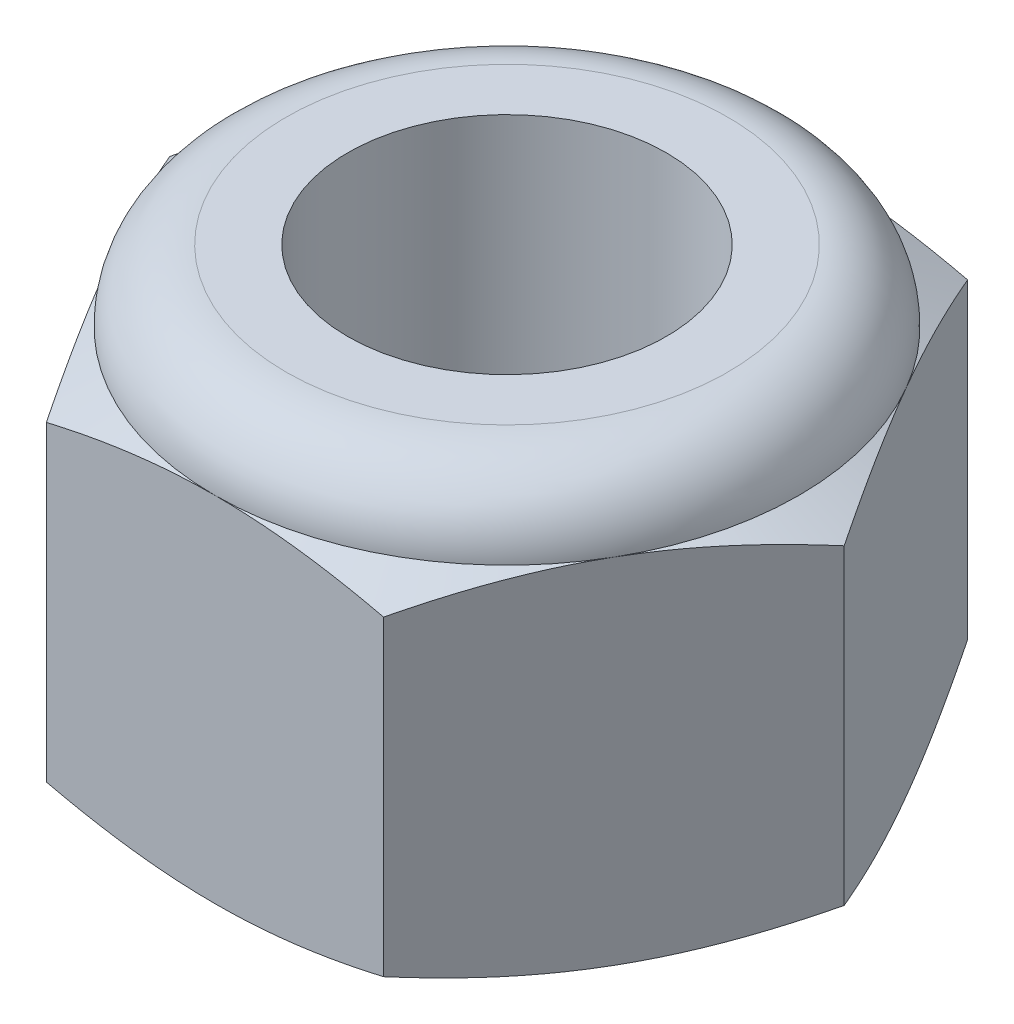
SolidWorks part; units mm, degrees
material "Stainless Steel (ferritic)"
ref_plane "Front" through (0, 0, 0) normal (0, 0, 1) x (1, 0, 0)
ref_plane "Top" through (0, 0, 0) normal (0, 1, 0) x (1, 0, 0)
ref_plane "Right" through (0, 0, 0) normal (1, 0, 0) x (0, 0, -1)
sketch "Sketch1" plane through (0, 0, 0) normal (0, 1, 0) x (1, 0, 0)
  line L1 (1.5877, 2.75) -> (-1.5877, 2.75)
  line L2 (-1.5877, 2.75) -> (-3.1754, 0)
  line L3 (-3.1754, 0) -> (-1.5877, -2.75)
  line L4 (-1.5877, -2.75) -> (1.5877, -2.75)
  line L5 (1.5877, -2.75) -> (3.1754, 0)
  line L6 (3.1754, 0) -> (1.5877, 2.75)
  circle A0 centre (0, 0) radius 2.75 construction
  circle A1 centre (0, 0) radius 1.5
  dimension "D2" = 3
  dimension "D1" = 5.5
extrude "Boss-Extrude1" add sketch "Sketch1" along normal blind 3.33
sketch "Sketch2" plane through (0, 3.33, 0) normal (0, 1, 0) x (1, 0, 0)
  circle A0 centre (0, 0) radius 2.75
  circle A1 centre (0, 0) radius 1.5 construction
  circle A2 centre (0, 0) radius 1.5
  dimension "D1" = 5.5
extrude "Boss-Extrude2" add sketch "Sketch2" along normal blind 0.67
fillet "Fillet1" radius 0.67 1 edges at (0, 4, 2.75)
sketch "Sketch3" plane through (-4.7631, 0, 0) normal (0, 0, -1) x (-1, 0, 0)
  line L0 (-1.5877, 3.33) -> (-1.5877, 3.1316)
  line L1 (-3.1754, 3.33) -> (-3.1754, 0) construction
  line L2 (-2.0131, 0) -> (-1.5877, 0.1984)
  line L3 (-3.1754, 1.665) -> (-1.5877, 1.665) construction
  line L4 (-1.5877, 3.33) -> (-1.5877, 0) construction
  line L5 (-1.5877, 0) -> (-1.5877, 0.1984)
  line L7 (-1.5877, 0) -> (-2.0131, 0)
  line L8 (-1.5877, 3.33) -> (-2.0131, 3.33)
  line L9 (-2.0131, 3.33) -> (-1.5877, 3.1316)
  dimension "D1" = 25
sketch "Sketch4" plane through (0, 0, 0) normal (0, 0, 1) x (1, 0, 0)
  line L0 (0, 0) -> (0, 2.9206) construction
  line L1 (-1.5877, 0) -> (1.5877, 0) construction
revolve "Cut-Revolve1" cut sketch "Sketch3" angle 360 about L0
